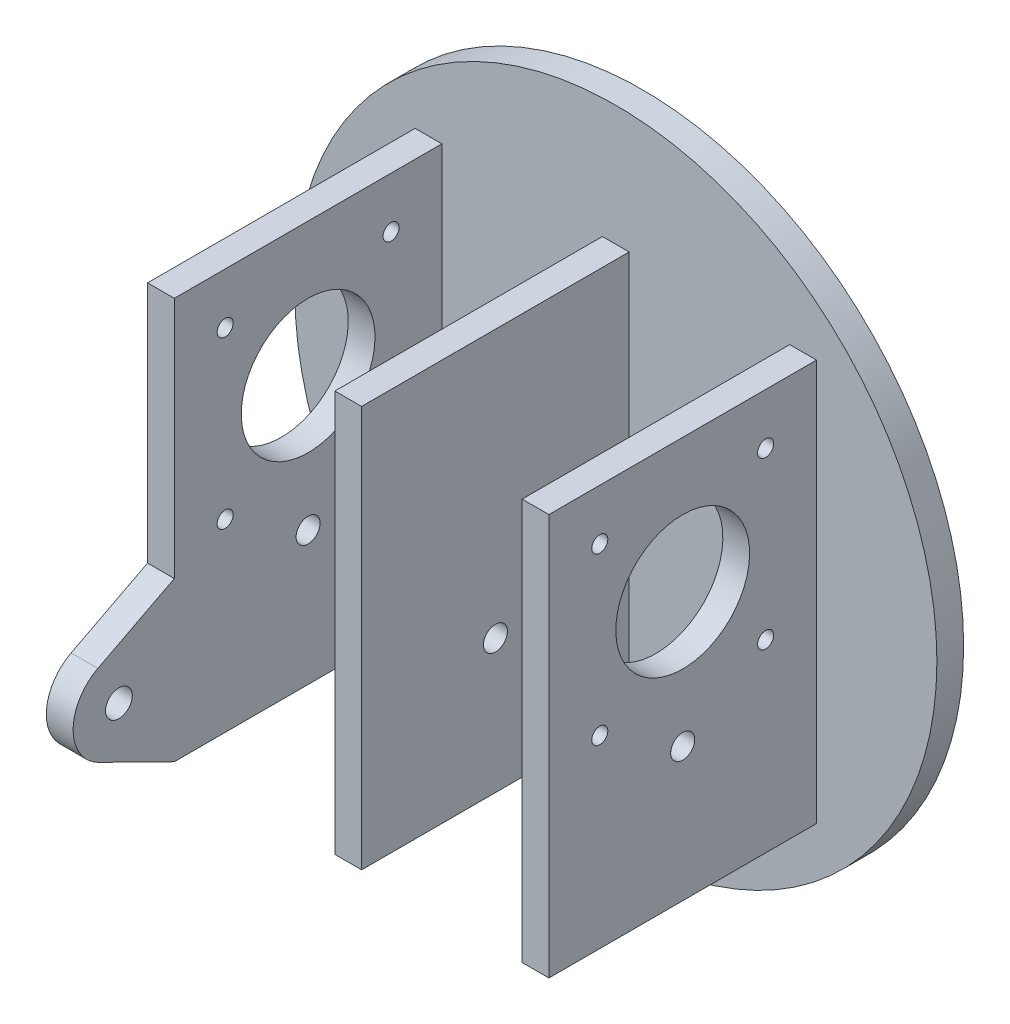
SolidWorks part; units mm, degrees
ref_plane "Front Plane" through (0, 0, 0) normal (0, 0, 1) x (1, 0, 0)
ref_plane "Top Plane" through (0, 0, 0) normal (0, 1, 0) x (1, 0, 0)
ref_plane "Right Plane" through (0, 0, 0) normal (1, 0, 0) x (0, 0, -1)
sketch "Sketch1" plane through (0, 0, 0) normal (0, 0, 1) x (1, 0, 0)
  circle A0 centre (0, 0) radius 60
  circle A1 centre (0, 0) radius 1.5
  dimension "D1" = 120
  dimension "D2" = 3
extrude "Boss-Extrude1" add sketch "Sketch1" along normal blind 5
sketch "Sketch2" plane through (0, 0, 0) normal (0, 0, -1) x (-1, 0, 0)
  line L0 (37.5, 37.5) -> (-37.5, -37.5) construction
  line L1 (-37.5, 37.5) -> (37.5, -37.5) construction
  line L3 (-37.5, 37.5) -> (-32.5, 37.5)
  line L4 (-37.5, 37.5) -> (-37.5, -37.5)
  line L5 (-37.5, -37.5) -> (-32.5, -37.5)
  line L6 (-32.5, 37.5) -> (-32.5, -37.5)
  line L7 (37.5, 37.5) -> (32.5, 37.5)
  line L8 (37.5, 37.5) -> (37.5, -37.5)
  line L9 (37.5, -37.5) -> (32.5, -37.5)
  line L10 (32.5, 37.5) -> (32.5, -37.5)
  line L11 (-2.5, -37.5) -> (2.5, -37.5)
  line L12 (-2.5, -37.5) -> (-2.5, 37.5)
  line L13 (-2.5, 37.5) -> (2.5, 37.5)
  line L14 (2.5, -37.5) -> (2.5, 37.5)
  line L15 (-2.5, -37.5) -> (2.5, 37.5) construction
  line L16 (-2.5, 37.5) -> (2.5, -37.5) construction
  point P7 (0, 0)
  dimension "D1" = 75
  dimension "D2" = 5
extrude "Boss-Extrude2" add sketch "Sketch2" along normal blind 50
sketch "Sketch3" plane through (32.5, 0, 0) normal (-1, 0, 0) x (0, 0, 1)
  line L0 (-50, -37.5) -> (0, 12.5) construction
  line L1 (-50, -37.5) -> (-50, 37.5) construction
  line L2 (-50, -37.5) -> (0, -37.5) construction
  line L3 (0, -37.5) -> (0, 37.5) construction
  line L4 (0, -37.5) -> (-50, 12.5) construction
  circle A0 centre (-40.5, 3) radius 1.5
  circle A1 centre (-9.5, 3) radius 1.5
  circle A2 centre (-9.5, -28) radius 1.5
  circle A3 centre (-40.5, -28) radius 1.5
  circle A4 centre (-25, -12.5) radius 12.5
  dimension "D2" = 3
  dimension "D4" = 25
  dimension "D1" = 45
  dimension "D3" = 31
extrude "Cut-Extrude1" cut sketch "Sketch3" against normal through all
sketch "Sketch5" plane through (-2.5, 0, 0) normal (-1, 0, 0) x (0, 0, 1)
  line L0 (-25, -37.5) -> (-25, 37.5) construction
  line L1 (-50, -37.5) -> (0, -37.5) construction
  line L2 (-50, 37.5) -> (0, 37.5) construction
  line L4 (-23.4125, -14.0875) -> (-26.5875, -14.0875)
  line L5 (-23.4125, -14.0875) -> (-23.4125, -10.9125)
  line L6 (-23.4125, -10.9125) -> (-26.5875, -10.9125)
  line L7 (-26.5875, -14.0875) -> (-26.5875, -10.9125)
  line L8 (-23.4125, -14.0875) -> (-26.5875, -10.9125) construction
  line L9 (-23.4125, -10.9125) -> (-26.5875, -14.0875) construction
  circle A0 centre (-25, -12.5) radius 2.2451
  circle A1 centre (-25, 12.5) radius 2.2451
  dimension "D3" = 3.175
  dimension "D1" = 25
  dimension "D2" = 25
extrude "Cut-Extrude4" cut sketch "Sketch5" against normal blind 53 and the other way through all contours A1 region at (-2.5, 12.5, -25)
sketch "Sketch6" plane through (-37.5, 0, 0) normal (-1, 0, 0) x (0, 0, 1)
  line L0 (-50, -37.5) -> (0, 12.5) construction
  line L1 (0, -37.5) -> (-50, 12.5) construction
  circle A0 centre (-40.5, 3) radius 1.5
  circle A1 centre (-9.5, 3) radius 1.5
  circle A2 centre (-9.5, -28) radius 1.5
  circle A3 centre (-40.5, -28) radius 1.5
  circle A4 centre (-25, -12.5) radius 12.5
  dimension "D1" = 3
  dimension "D3" = 25
  dimension "D2" = 31
extrude "Cut-Extrude5" cut sketch "Sketch6" against normal up to surface (5 mm away) up to face at (-32.5, 10.2549, -25)
sketch "Sketch7" plane through (-37.5, 0, 0) normal (-1, 0, 0) x (0, 0, 1)
  line L0 (-25, -12.5) -> (-60.3553, 22.8553) construction
  line L1 (0, 60) -> (0, -60) construction
  line L2 (-50, 37.5) -> (-64.1385, 30.5347)
  line L3 (-64.2907, 15.2528) -> (-50, 7.8553)
  line L4 (-50, -37.5) -> (-50, 37.5) construction
  line L6 (-50, 7.8553) -> (-50, 37.5)
  circle A2 centre (-25, -12.5) radius 12.5 construction
  circle A3 centre (-60.3553, 22.8553) radius 2.5
  arc A4 (-64.2907, 15.2528) -> (-64.1385, 30.5347) centre (-60.3553, 22.8553) cw
  dimension "D3" = 5
  dimension "D1" = 50
  dimension "D2" = 45
  dimension "D4" = 15
extrude "Boss-Extrude4" add sketch "Sketch7" against normal blind 5
move or copy body "Body-Move/Copy1" bodies to move or copy 109 copy no rotation origin (0, 0, -31.958) rotation axis (1, 0, 0) rotation angle 180
move or copy body "Body-Move/Copy2" bodies to move or copy 110 copy no translate (0, 0, 68.916)
